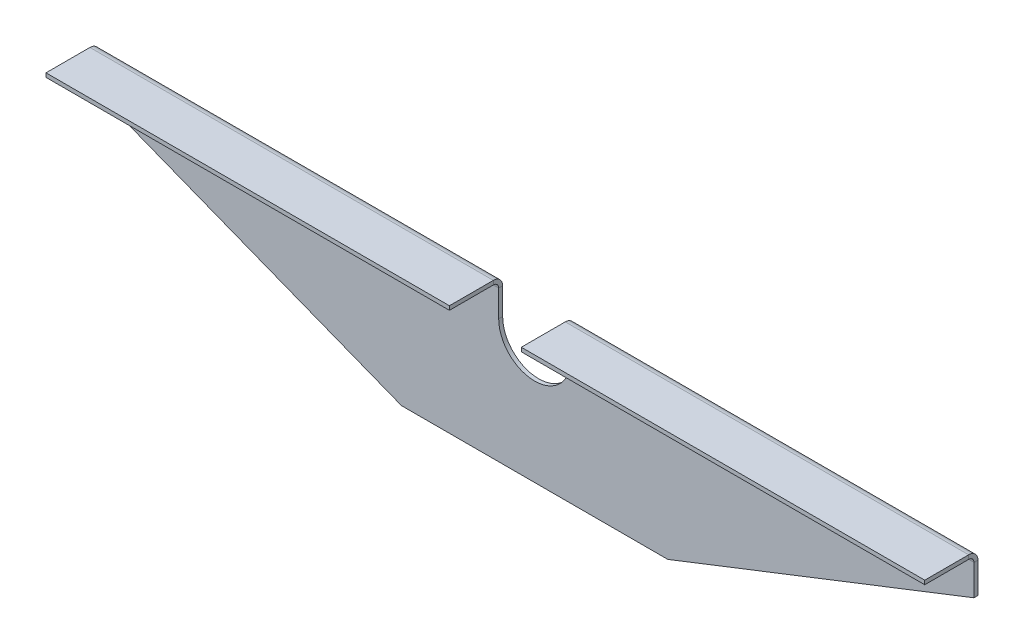
SolidWorks part; units mm, degrees
note: The reader was unsure of these and kept them because the rebuilt part matched: flange length of "Edge-Flange1".
material "Galvanized Steel"
ref_plane "Front Plane" through (0, 0, 0) normal (0, 0, 1) x (1, 0, 0)
ref_plane "Top Plane" through (0, 0, 0) normal (0, 1, 0) x (1, 0, 0)
ref_plane "Right Plane" through (0, 0, 0) normal (1, 0, 0) x (0, 0, -1)
sketch "Sketch1" plane through (0, 0, 0) normal (0, 0, 1) x (1, 0, 0)
  line L0 (-165, 10) -> (165, 10)
  line L1 (165, 10) -> (165, -5)
  line L2 (165, -5) -> (50, -50)
  line L3 (50, -50) -> (-50, -50)
  line L4 (-50, -50) -> (-165, -5)
  line L5 (-165, -5) -> (-165, 10)
  point P7 (0, 10)
  point P9 (0, -50)
  dimension "D1" = 330
  dimension "D2" = 15
  dimension "D3" = 60
  dimension "D4" = 15
  dimension "D5" = 50
  dimension "D6" = 100
base flange "Base-Flange2" sketch "Sketch1" thickness 1.5 reverse thickness direction no parameters "D1"=2
edge flange "Edge-Flange1" sketch "Sketch12" flange angle 90 flange length 20 flange position material inside bend radius 2 thickness 1.5 relief obround parameters "D6"=10
sketch "Sketch12" plane through (0, 10, 0) normal (0, -1, 0) x (1, 0, 0)
  line L2 (-165, 0) -> (-165, 18.5)
  line L3 (-165, 18.5) -> (165, 18.5)
  line L4 (165, 18.5) -> (165, 0)
  line L5 (165, 0) -> (-165, 0) construction
  line L6 (165, 0) -> (-165, 0)
bend "EdgeBend1" bend radius 2 bend angle 90 parameters "D5"=1
sketch "Sketch13" plane through (0, 0, 0) normal (0, 0, 1) x (1, 0, 0)
  line L0 (-13.5, -3.5) -> (-13.5, 21.0126)
  line L2 (13.5, -3.5) -> (13.5, 21.0126)
  line L3 (13.5, 21.0126) -> (-13.5, 21.0126)
  arc A0 (-13.5, -3.5) -> (13.5, -3.5) centre (0, -3.5) ccw
  dimension "D1" = 27
extrude "Cut-Extrude1" cut sketch "Sketch13" along normal through all and the other way blind 10 contours L3 L0 A0 L2 normal cut yes
sketch "Bend-Lines3" [suppressed] plane through (0, 0, 0) normal (0, 1, 0) x (1, 0, 0)
sketch "Bounding-Box3" [suppressed] plane through (0, 0, 0) normal (0, 1, 0) x (1, 0, 0)
sheet metal parameters "Sheet-Metal2" thickness 1.5 parameters "D1"=2
flat pattern "Flat-Pattern2" [suppressed]
sketch "Bend-Lines4" plane through (0, 0, 0) normal (0, 1, 0) x (1, 0, 0)
sketch3d "Bounding-Box4" [suppressed]
  line L0 (165, -50, 0) -> (-165, -50, 0) construction
  line L1 (165, 10, 0) -> (-165, 10, 0) construction
  line L2 (165, -50, 0) -> (165, 10, 0) construction
  line L3 (-165, -50, 0) -> (-165, 10, 0) construction
sheet metal parameters "Sheet-Metal3" thickness 1.5 parameters "D1"=2
flat pattern "Flat-Pattern2"
sketch "Bend-Lines4" plane through (0, 0, 0) normal (0, 0, 1) x (1, 0, 0)
  line L0 (165, 8.6598) -> (-165, 8.6598) construction
  line L1 (165, 8.6598) -> (-165, 8.6598) construction
sketch3d "Bounding-Box4" [suppressed]
  line L0 (-165, -50, 0) -> (165, -50, 0) construction
  line L1 (-165, 27.3197, 0) -> (165, 27.3197, 0) construction
  line L2 (-165, -50, 0) -> (-165, 27.3197, 0) construction
  line L3 (165, -50, 0) -> (165, 27.3197, 0) construction
bend of the flat pattern "Flatten-<EdgeBend1>1"
sheet metal parameters "Sheet-Metal4" thickness 1.5 parameters "D1"=2
flat pattern "Flat-Pattern2"
sketch "Bend-Lines4" plane through (0, 0, 0) normal (0, 0, 1) x (1, 0, 0)
  line L0 (165, 8.6598) -> (13.5, 8.6598) construction
  line L1 (165, 8.6598) -> (13.5, 8.6598) construction
  line L2 (-13.5, 8.6598) -> (-165, 8.6598) construction
sketch3d "Bounding-Box4" [suppressed]
  line L0 (-165, -50, 0) -> (165, -50, 0) construction
  line L1 (-165, 27.3197, 0) -> (165, 27.3197, 0) construction
  line L2 (-165, -50, 0) -> (-165, 27.3197, 0) construction
  line L3 (165, -50, 0) -> (165, 27.3197, 0) construction
bend of the flat pattern "Flatten-<EdgeBend1>1"
